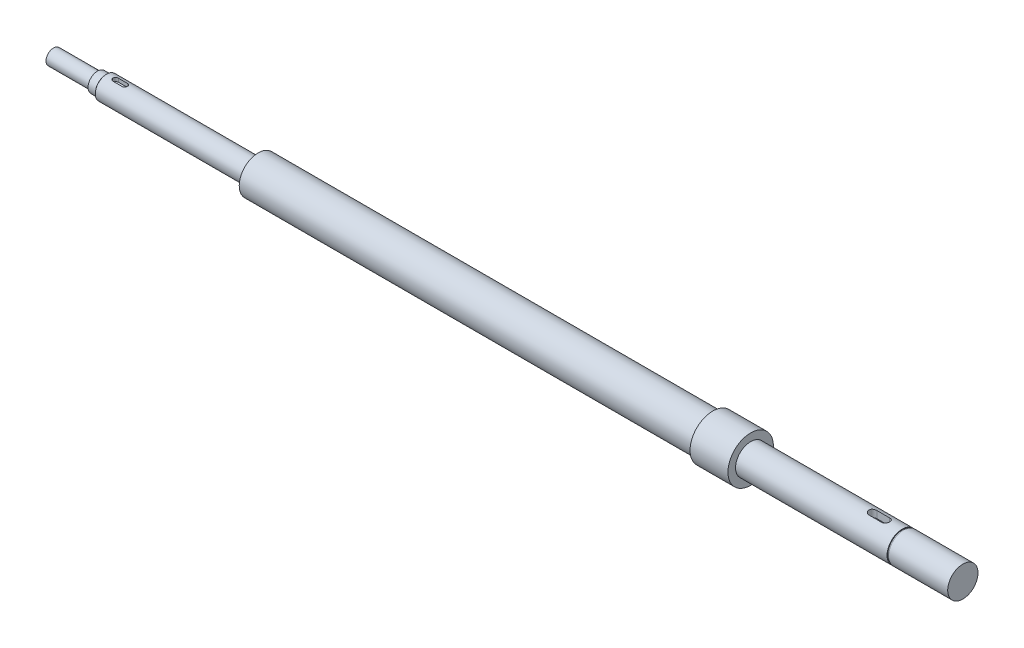
SolidWorks part; units mm, degrees
ref_plane "Front Plane" through (0, 0, 0) normal (0, 0, 1) x (1, 0, 0)
ref_plane "Top Plane" through (0, 0, 0) normal (0, 1, 0) x (1, 0, 0)
ref_plane "Right Plane" through (0, 0, 0) normal (1, 0, 0) x (0, 0, -1)
sketch "Sketch1" plane through (0, 0, 0) normal (1, 0, 0) x (0, 0, -1)
  circle A0 centre (0, 0) radius 500
extrude "Boss-Extrude1" add sketch "Sketch1" along normal blind 600
sketch "Sketch2" plane through (0, 0, 0) normal (-1, 0, 0) x (0, 0, 1)
  circle A0 centre (0, 0) radius 5
extrude "Cut-Extrude1" cut sketch "Sketch2" against normal blind 29 flip side to cut
sketch "Sketch3" plane through (29, 0, 0) normal (-1, 0, 0) x (0, 0, 1)
  circle A0 centre (0, 0) radius 6.25
extrude "Cut-Extrude2" cut sketch "Sketch3" against normal blind 5 flip side to cut
sketch "Sketch4" plane through (34, 0, 0) normal (-1, 0, 0) x (0, 0, 1)
  circle A0 centre (0, 0) radius 5.75
extrude "Cut-Extrude3" cut sketch "Sketch4" against normal blind 1 flip side to cut
sketch "Sketch5" plane through (35, 0, 0) normal (-1, 0, 0) x (0, 0, 1)
  circle A0 centre (0, 0) radius 7.5
extrude "Cut-Extrude4" cut sketch "Sketch5" against normal blind 100 flip side to cut
sketch "Sketch6" plane through (135, 0, 0) normal (-1, 0, 0) x (0, 0, 1)
  circle A0 centre (0, 0) radius 12.5
extrude "Cut-Extrude5" cut sketch "Sketch6" against normal blind 300 flip side to cut
sketch "Sketch7" plane through (435, 0, 0) normal (-1, 0, 0) x (0, 0, 1)
  circle A0 centre (0, 0) radius 15
extrude "Cut-Extrude6" cut sketch "Sketch7" against normal blind 25 flip side to cut
sketch "Sketch8" plane through (460, 0, 0) normal (-1, 0, 0) x (0, 0, 1)
  circle A0 centre (0, 0) radius 10
extrude "Cut-Extrude7" cut sketch "Sketch8" against normal blind 100 flip side to cut
sketch "Sketch9" plane through (560, 0, 0) normal (-1, 0, 0) x (0, 0, 1)
  circle A0 centre (0, 0) radius 9.5
extrude "Cut-Extrude8" cut sketch "Sketch9" against normal blind 1 flip side to cut
sketch "Sketch10" plane through (561, 0, 0) normal (-1, 0, 0) x (0, 0, 1)
  circle A0 centre (0, 0) radius 10
extrude "Cut-Extrude10" cut sketch "Sketch10" against normal up to surface (39 mm away) flip side to cut up to face at (600, 0, -500)
ref_plane "Plane1" through (0, 30, 0) normal (0, 1, 0) x (1, 0, 0)
sketch "Sketch14" plane through (0, 30, 0) normal (0, 1, 0) x (1, 0, 0)
  line L0 (41.0357, 0) -> (47.0877, 0) construction
  line L1 (41.0357, 1.762) -> (47.0877, 1.762)
  line L2 (41.0357, -1.762) -> (47.0877, -1.762)
  line L3 (540.6675, 0) -> (549.1548, 0) construction
  line L4 (540.6675, 2.5986) -> (549.1548, 2.5986)
  line L5 (540.6675, -2.5986) -> (549.1548, -2.5986)
  arc A0 (41.0357, 1.762) -> (41.0357, -1.762) centre (41.0357, 0) ccw
  arc A1 (47.0877, -1.762) -> (47.0877, 1.762) centre (47.0877, 0) ccw
  arc A2 (540.6675, 2.5986) -> (540.6675, -2.5986) centre (540.6675, 0) ccw
  arc A3 (549.1548, -2.5986) -> (549.1548, 2.5986) centre (549.1548, 0) ccw
  point P2 (44.0617, 0)
  point P10 (544.9112, 0)
  point P15 (0, 0)
  point P16 (527.8639, 0)
split line "Split Line1"
extrude "Cut-Extrude11" cut sketch "Sketch14<3>" against normal blind 25
sketch "Sketch14<3>" plane through (0, 30, 0) normal (0, 1, 0) x (1, 0, 0) same geometry as "Sketch14"
